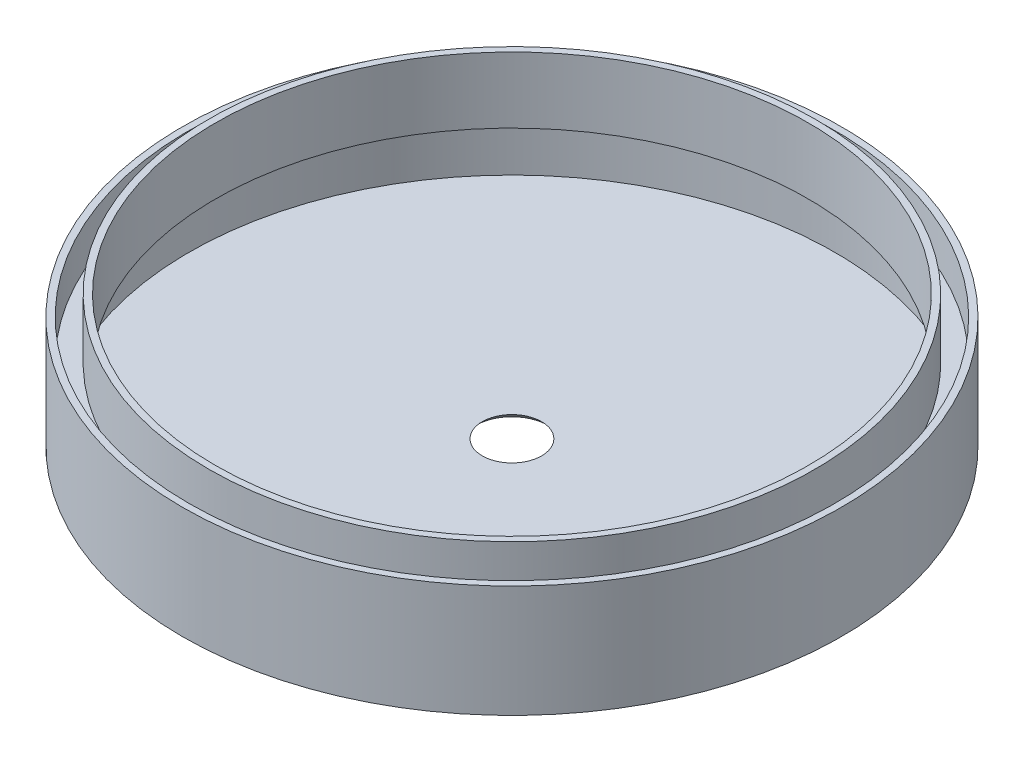
SolidWorks part; units mm, degrees
ref_plane "Plan de face" through (0, 0, 0) normal (0, 0, 1) x (1, 0, 0)
ref_plane "Plan de dessus" through (0, 0, 0) normal (0, 1, 0) x (1, 0, 0)
ref_plane "Plan de droite" through (0, 0, 0) normal (1, 0, 0) x (0, 0, -1)
sketch "Esquisse1" plane through (0, 0, 0) normal (0, 1, 0) x (1, 0, 0)
  circle A0 centre (0, 0) radius 50
  dimension "D1" = 100
extrude "Boss.-Extru.1" add sketch "Esquisse1" along normal blind 17
shell "Coque1" thickness 1 removed face at (0, 17, 50)
sketch "Esquisse2" plane through (0, 0, 0) normal (0, 1, 0) x (1, 0, 0)
  circle A0 centre (0, 0) radius 4.5
  dimension "D1" = 9
extrude "Enlèv. mat.-Extru.3" cut sketch "Esquisse2" along normal through all
chamfer "Chanfrein1" distance 1 angle 45 1 edges at (0, 0, 4.5)
ref_plane "Plan1" through (0, 10, 0) normal (0, 1, 0) x (1, 0, 0)
sketch "Esquisse3" plane through (0, 10, 0) normal (0, 1, 0) x (1, 0, 0)
  circle A0 centre (0, 0) radius 50
  circle A1 centre (0, 0) radius 45
  circle A2 centre (0, 0) radius 50 construction
  dimension "D1" = 5
extrude "Boss.-Extru.2" add sketch "Esquisse3" along normal blind 1
sketch "Esquisse4" plane through (0, 10, 0) normal (0, 1, 0) x (1, 0, 0)
  circle A0 centre (0, 0) radius 45
  circle A1 centre (0, 0) radius 46
  circle A2 centre (0, 0) radius 45 construction
  dimension "D1" = 1
extrude "Boss.-Extru.3" add sketch "Esquisse4" along normal blind 10
